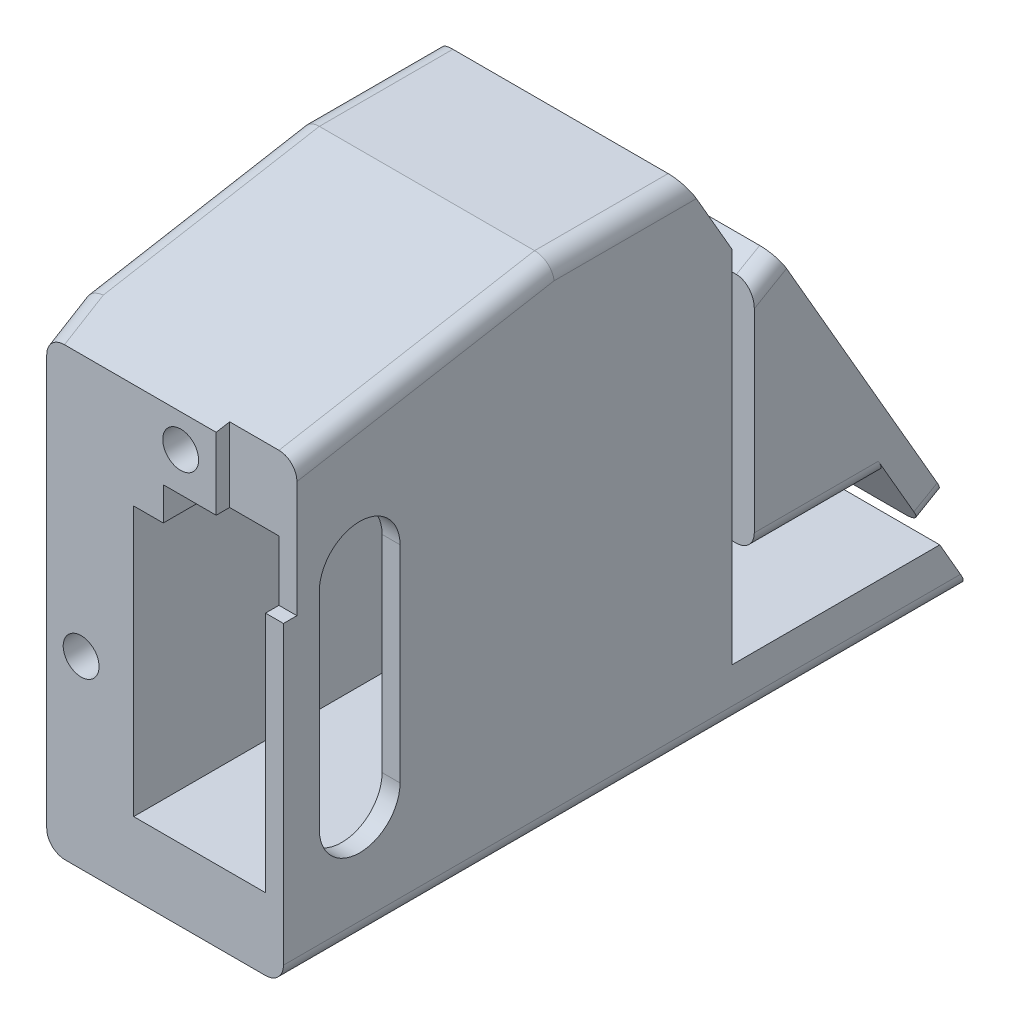
SolidWorks part; units mm, degrees
ref_plane "Plan de face" through (0, 0, 0) normal (0, 0, 1) x (1, 0, 0)
ref_plane "Plan de dessus" through (0, 0, 0) normal (0, 1, 0) x (1, 0, 0)
ref_plane "Plan de droite" through (0, 0, 0) normal (1, 0, 0) x (0, 0, -1)
sketch "taille_batterie" plane through (0, 0, 0) normal (0, 0, 1) x (1, 0, 0)
  line L1 (-7, -16.5) -> (7, -16.5)
  line L2 (-7, -16.5) -> (-7, 16.5)
  line L3 (-7, 16.5) -> (7, 16.5)
  line L4 (7, -16.5) -> (7, 16.5)
  line L5 (-7, -16.5) -> (7, 16.5) construction
  line L6 (-7, 16.5) -> (7, -16.5) construction
  line L7 (-19, 30.5) -> (9, 30.5)
  line L8 (-19, 30.5) -> (-19, -24.5)
  line L9 (-19, -24.5) -> (9, -24.5)
  line L10 (9, 30.5) -> (9, -24.5)
  point P0 (0, 0)
  point P10 (0, 0)
  point P11 (0, 0)
  point P12 (0, 0)
  point P13 (0, 0)
  point P14 (0, 0)
  point P15 (0, 0)
  dimension "D1" = 33
  dimension "D2" = 14
  dimension "D3" = 2
  dimension "D4" = 8
  dimension "D5" = 12
  dimension "D6" = 14
ref_plane "Plan_arrière_batterie" through (0, 0, -53) normal (0, 0, 1) x (1, 0, 0)
sketch "Esquisse2" plane through (0, 0, 0) normal (1, 0, 0) x (0, 0, -1)
  line L0 (0, -24.5) -> (0, 30.5)
  line L1 (0, 30.5) -> (44.8908, 30.5)
  line L2 (44.8908, 30.5) -> (76.6451, -24.5)
  line L3 (76.6451, -24.5) -> (0, -24.5)
  line L4 (0, 0) -> (62.5, 0) construction
  point P9 (0, 0)
  dimension "D3" = 120
  dimension "D4" = 62.5
extrude "corps" add sketch "Esquisse2" along normal up to vertex (9 mm away) and the other way up to vertex (19 mm away) up to point (9, 30.5, 0) other way up to point (-19, 30.5, 0)
ref_plane "Plan_coupe_arriere" through (0, 27.0633, -46.875) normal (0, -0.5, 0.866) x (0, -0.866, -0.5)
sketch "Esquisse3" plane through (0, 0, 0) normal (0, 0, 1) x (1, 0, 0)
  line L2 (-7.7, -16.5) -> (7, -16.5)
  line L3 (7, -16.5) -> (7, 17.2)
  line L4 (-7.7, -16.5) -> (-7.7, 17.2)
  line L5 (-7.7, 17.2) -> (7, 17.2)
  line L6 (-7.7, -16.5) -> (-7.7, 17.2)
  line L7 (-7.7, 17.2) -> (7, 17.2)
  dimension "D1" = 0.7
extrude "cavite_batterie" cut sketch "Esquisse3" against normal through all
hole_wizard "Diamètre du perçage Ø4.0 (4)1" positions "Esquisse4" profile "Esquisse5" hole size "Ø4.0" standard "ISO"
sketch "Esquisse4" plane through (0, 0, 0) normal (0, 0, 1) x (1, 0, 0)
  point P0 (-2.4576, 21.55)
  point P2 (-13.5576, -3.95)
  point P5 (-13.5576, -3.95)
  point P7 (-2.4576, 21.55)
  point P9 (0, 0)
  point P10 (0, 0)
sketch "Esquisse5" plane through (-2.4576, 21.55, 0) normal (1, 0, 0) x (0, -1, 0)
  line L0 (0, 0) -> (0, 6.7)
  line L1 (0, 6.7) -> (2, 6.7)
  line L2 (2, 6.7) -> (2, 0)
  line L5 (2, 0) -> (0, 0)
  line L10 (0, 6.7) -> (-2, 6.7) construction
  line L11 (0, -6.35) -> (0, 107.95) construction
  dimension "Diamètre du perçage" = 4
  dimension "Profondeur du perçage" = 6.7
  dimension "Angle de pointe" = 180
hole_wizard "Diamètre du perçage Ø4.0 (4)2" positions "Esquisse6" profile "Esquisse7" hole size "Ø4.0" standard "ISO"
sketch "Esquisse6" plane through (0, 27.0633, -46.875) normal (0, 0.5, -0.866) x (-1, 0, 0)
  line L0 (13, -26.8459) -> (13, -45.8459) construction
  line L2 (7.7, -30.8459) -> (13, -30.8459) construction
  line L3 (7.7, -11.3892) -> (7.7, -50.3026) construction
  point P0 (13, -26.8459)
  point P2 (13, -45.8459)
  point P15 (0, 0)
  dimension "D1" = 4
  dimension "D2" = 13
  dimension "D3" = 15
sketch "Esquisse7" plane through (-13, 3.8141, -60.2979) normal (1, 0, 0) x (0, 0.866, 0.5)
  line L0 (0, 0) -> (0, 6.7)
  line L1 (0, 6.7) -> (2, 6.7)
  line L2 (2, 6.7) -> (2, 0)
  line L5 (2, 0) -> (0, 0)
  line L10 (0, 6.7) -> (-2, 6.7) construction
  line L11 (0, -6.35) -> (0, 107.95) construction
  dimension "Diamètre du perçage" = 4
  dimension "Profondeur du perçage" = 6.7
  dimension "Angle de pointe" = 180
sketch "Esquisse8" plane through (-7.7, 0, 0) normal (1, 0, 0) x (0, 0, -1)
  line L0 (44.8908, 30.5) -> (76.6451, -24.5) construction
  line L1 (50, 21.6506) -> (76.6451, 21.6506)
  line L2 (50, 21.6506) -> (50, -18.5)
  line L3 (50, -18.5) -> (76.6451, -18.5)
  line L4 (76.6451, 21.6506) -> (76.6451, -18.5)
  line L5 (8.5, 11.6) -> (8.5, -11.4) construction
  line L6 (13, 11.6) -> (13, -11.4)
  line L7 (4, 11.6) -> (4, -11.4)
  line L8 (53, 21.6506) -> (53, 16.4545) construction
  line L9 (53, 14.3) -> (53, -14.3) construction
  line L10 (53, 16.4545) -> (53, -18.5) construction
  line L11 (31.75, 53.2606) -> (62, 0.866) construction
  arc A0 (13, 11.6) -> (4, 11.6) centre (8.5, 11.6) ccw
  arc A1 (4, -11.4) -> (13, -11.4) centre (8.5, -11.4) ccw
  point P13 (8.5, 0.1)
  point P18 (51.5218, 7.8261)
  point P24 (0, 0)
  point P25 (0, 0)
  dimension "D1" = 3
  dimension "D2" = 2
extrude "degagement_trappe et connecteur" cut sketch "Esquisse8" along normal through all
chamfer "Chanfrein1" distance 2 angle 45 3 edges at (-0.35, -16.5, -50) (7, 0.35, -50) (-0.35, 17.2, -50)
sketch "Esquisse9" plane through (0, 0, 0) normal (0, 0, 1) x (1, 0, 0)
  line L1 (-7.7, 17.2) -> (-4.4, 17.2)
  line L2 (-7.7, 17.2) -> (-7.7, 13.5)
  line L3 (-7.7, 13.5) -> (-4.4, 13.5)
  line L4 (-4.4, 17.2) -> (-4.4, 13.5)
  dimension "D1" = 3.3
  dimension "D2" = 3.7
extrude "detrompeur_batterie" add sketch "Esquisse9" against normal blind 7
chamfer "Chanfrein2" distance 30 angle 10 1 edges at (-5, 30.5, 0) first distance on face at (-5, 30.5, -22.4454)
chamfer "Chanfrein3" distance 6 angle 15 1 edges at (-19, 0.3551, 0) first distance on face at (-19, 7.442, -30.3072)
sketch "Esquisse10" plane through (0, 0, 0) normal (0, 0, 1) x (1, 0, 0)
  line L1 (1.5, 30.5) -> (9, 30.5)
  line L2 (1.5, 30.5) -> (1.5, 10.5)
  line L3 (1.5, 10.5) -> (9, 10.5)
  line L4 (9, 30.5) -> (9, 10.5)
  point P4 (9, 30.5)
  point P5 (6.226, 29.0389)
  point P6 (8.25, 30.2082)
  dimension "D1" = 20
  dimension "D2" = 7.5
extrude "degagement_pin_interrupteur" cut sketch "Esquisse10" against normal blind 1.5
fillet "Congé2" radius 2 8 edges at (9, -24.5, -38.3225) (-19, -24.5, -41.3225) (-18.1962, -24.5, -3) (-18.1962, 25.7392, -3) (9, 27.9873, -15.75) (9, 30.5, -37.4454) (-19, 30.5, -37.4454) (-19, 28.3841, -18)
sketch "Esquisse11" plane through (0, 27.0633, -46.875) normal (0, -0.5, 0.866) x (0, -0.866, -0.5)
  line L0 (26.8459, -13) -> (45.8459, -13) construction
  line L1 (49.8459, 8.5) -> (12.25, 8.5)
  line L2 (49.8459, 8.5) -> (49.8459, -19)
  line L3 (49.8459, -19) -> (12.25, -19)
  line L4 (12.25, 8.5) -> (12.25, -19)
  point P4 (0, 0)
  point P5 (0, 0)
  point P15 (0, 0)
  point P16 (0, 0)
  point P17 (11.213, 8.5)
  dimension "D2" = 4
  dimension "D1" = 0.5
extrude "corps_butee_1" add sketch "Esquisse11" against normal blind 3 separate body
sketch "Esquisse12" plane through (-7.7, 0, 0) normal (1, 0, 0) x (0, 0, -1)
  line L0 (53, 16.4545) -> (53, -9.5)
  line L1 (53, -9.5) -> (67.9848, -9.5)
  line L2 (67.9848, -9.5) -> (53, 16.4545)
  line L3 (53, 14.3) -> (53, -14.3) construction
  line L4 (31.75, 53.2606) -> (62, 0.866) construction
  dimension "D1" = 7
extrude "corps_butee_2" add sketch "Esquisse12" along normal up to surface (16.2 mm away) from offset 0.5 up to face at (8.5, 0.925, -63.698)
sketch "Esquisse14" plane through (0, 0, 0) normal (1, 0, 0) x (0, 0, -1)
  line L0 (55.3453, 4.3923) -> (60.4171, -4.3923)
  line L1 (64.7472, -6.8923) -> (69.9434, -6.8923)
  line L2 (69.9434, -6.8923) -> (64.9434, 1.7679)
  line L3 (64.9434, 1.7679) -> (62.9434, 5.2321) construction
  line L4 (62.9434, 5.2321) -> (57.9434, 13.8923)
  line L5 (57.9434, 13.8923) -> (55.3453, 9.3923)
  line L6 (31.75, 53.2606) -> (62, 0.866) construction
  line L7 (62.2113, 2.5) -> (63.9434, 3.5) construction
  line L8 (62.2113, 2.5) -> (57.8812, 0) construction
  line L9 (57.8812, 0) -> (0, 0) construction
  arc A2 (62.9434, 5.2321) -> (64.9434, 1.7679) centre (63.9434, 3.5) ccw
  arc A3 (60.4171, -4.3923) -> (64.7472, -6.8923) centre (64.7472, -1.8923) ccw
  arc A4 (55.3453, 4.3923) -> (55.3453, 9.3923) centre (59.6754, 6.8923) cw
  dimension "D1" = 3
  dimension "D3" = 2
  dimension "D6" = 5
  dimension "D2" = 4
  dimension "D4" = 5
  dimension "D5" = 10
extrude "accroche_trappe" cut sketch "Esquisse14" against normal mid plane 12
sketch "Esquisse13" plane through (0, 27.0633, -46.875) normal (0, -0.5, 0.866) x (0, -0.866, -0.5)
  line L0 (45.8459, -11.4) -> (41.8459, -11.4)
  line L1 (45.8459, -14.6) -> (41.8459, -14.6)
  line L4 (45.8459, -13) -> (41.8459, -13) construction
  line L5 (26.8459, -11.4) -> (22.8459, -11.4)
  line L6 (26.8459, -14.6) -> (22.8459, -14.6)
  line L7 (41.8459, -11.4) -> (41.8459, -14.6) construction
  line L8 (41.8459, -13) -> (38.8459, -13) construction
  line L9 (26.8459, -13) -> (22.8459, -13) construction
  line L10 (22.8459, -11.4) -> (22.8459, -14.6) construction
  line L11 (22.8459, -13) -> (19.8459, -13) construction
  arc A1 (45.8459, -11.4) -> (45.8459, -14.6) centre (45.8459, -13) cw
  arc A3 (41.8459, -11.4) -> (41.8459, -14.6) centre (38.8459, -13) ccw
  arc A5 (26.8459, -11.4) -> (26.8459, -14.6) centre (26.8459, -13) cw
  arc A6 (22.8459, -11.4) -> (22.8459, -14.6) centre (19.8459, -13) ccw
  point P12 (14.8092, -13.6)
  point P13 (0, 0)
  point P14 (25.0683, -23.7579)
  point P16 (18.6064, -11.6096)
  point P17 (42.8575, -13.6)
  point P18 (35.5553, -12.6652)
  point P21 (0, 0)
  point P22 (15.8906, -11.6096)
  point P24 (0, 0)
  point P25 (28.7139, -21.2436)
  point P26 (27.8967, -12.6454)
  dimension "D1" = 4
  dimension "D2" = 7
  dimension "D3" = 1.6
  dimension "D4" = 7
  dimension "D5" = 1.6
  dimension "D6" = 4
extrude "trou_de_serrure" cut sketch "Esquisse13" against normal through all
fillet "Congé1" radius 2 10 edges at (8.5, 17.2045, -54.299) (8.5, -9.5, -60.4924) (-7.2, -9.5, -60.4924) (8.5, -15.3545, -73.097) (-19, -15.3545, -73.097) (-19, 17.2045, -54.299) (-11.4, 8.0282, -59.597) (-11.4, -8.4263, -69.097) (-14.6, -8.4263, -69.097) (-14.6, 8.0282, -59.597)
